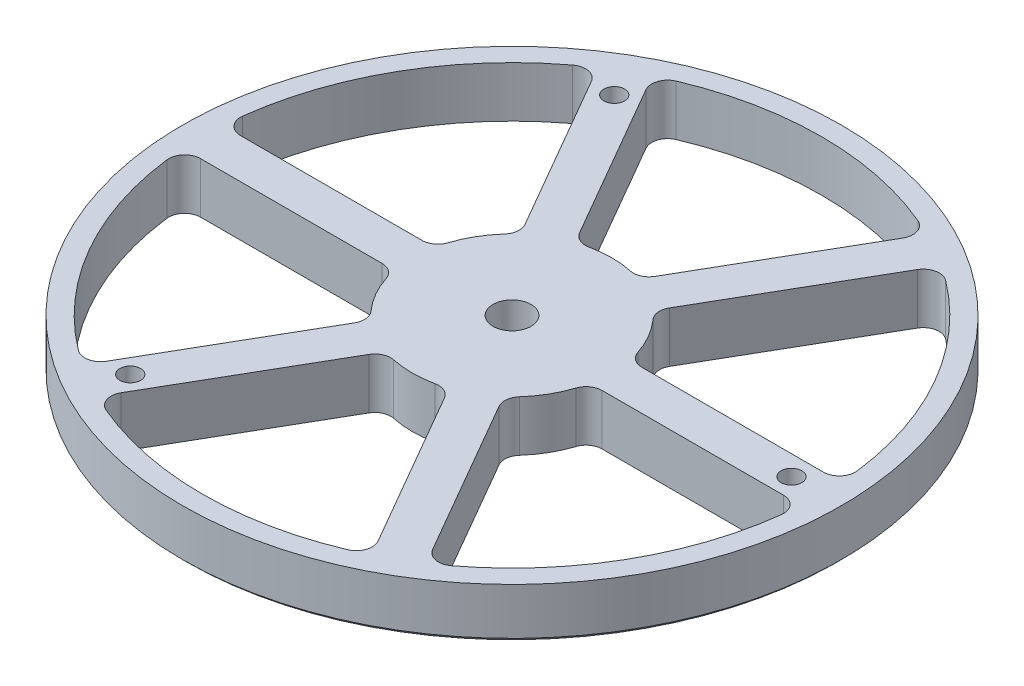
SolidWorks part; units mm, degrees
material "6061-T6 (SS)"
ref_plane "Front Plane" through (0, 0, 0) normal (0, 0, 1) x (1, 0, 0)
ref_plane "Top Plane" through (0, 0, 0) normal (0, 1, 0) x (1, 0, 0)
ref_plane "Right Plane" through (0, 0, 0) normal (1, 0, 0) x (0, 0, -1)
sketch "Sketch2" plane through (0, 0, 0) normal (1, 0, 0) x (0, 0, -1)
  line L0 (0, 0) -> (-82.55, 0)
  line L1 (-82.55, 0) -> (-82.55, 12.7)
  line L2 (-82.55, 12.7) -> (0, 12.7)
  line L5 (0, 12.7) -> (0, 0)
  dimension "D1" = 82.55
  dimension "D2" = 12.7
ref_axis "Axis1" through (0, -0.75, 0) along (0, 1, 0)
revolve "Revolve1" add sketch "Sketch2" angle 360 about axis through (0, -0.75, 0) along (0, 1, 0)
hole_wizard "#6 (0.204) Diameter Hole1" positions "Sketch6" profile "Sketch7" hole size "#6" standard "ANSI Inch" end condition through all
sketch "Sketch6" plane through (0, 12.7, 0) normal (0, 1, 0) x (1, 0, 0)
  line L0 (0, 0) -> (-69.8201, 120.932) construction
  line L2 (0, 0) -> (0, 109.0908) construction
  point P0 (-35, 60.6218)
  dimension "D1" = 30
  dimension "D2" = 70
sketch "Sketch7" plane through (-35, 12.7, -60.6218) normal (1, 0, 0) x (0, 0, 1)
  line L0 (0, 0) -> (0, 12.7)
  line L1 (0, 12.7) -> (2.5908, 12.7)
  line L2 (2.5908, 12.7) -> (2.5908, 0)
  line L5 (2.5908, 0) -> (0, 0)
  line L11 (0, -6.35) -> (0, 107.95) construction
  dimension "Thru Hole Dia." = 5.1816
  dimension "Thru Hole Depth" = 12.7
pattern_circular "CirPattern3" count 3 over 360 about axis through (0, -0.75, 0) along (0, 1, 0) of "#6 (0.204) Diameter Hole1"
sketch "Sketch8" plane through (0, 12.7, 0) normal (0, 1, 0) x (1, 0, 0)
  line L4 (0, 0) -> (0, 93.9995) construction
  line L5 (0, 0) -> (113.8372, 0) construction
  line L6 (-7.9173, 23.7132) -> (-34.3642, 69.5205)
  line L7 (7.9173, 23.7132) -> (34.3642, 69.5205)
  line L8 (0, 0) -> (-35, 60.6218) construction
  arc A0 (-7.9173, 23.7132) -> (7.9173, 23.7132) centre (0, 0) cw
  arc A1 (-34.3642, 69.5205) -> (34.3642, 69.5205) centre (0, 0) cw
  circle A2 centre (0, 0) radius 82.55 construction
  dimension "D1" = 25
  dimension "D2" = 5
  dimension "D3" = 5
extrude "Cut-Extrude1" cut sketch "Sketch8" against normal through all
fillet "Fillet1" radius 4 4 edges at (7.9173, 6.35, -23.7132) (34.3642, 6.35, -69.5205) (-7.9173, 6.35, -23.7132) (-34.3642, 6.35, -69.5205)
pattern_circular "CirPattern4" count 6 over 360 about axis through (0, -0.75, 0) along (0, 1, 0) of "Cut-Extrude1", "Fillet1"
chamfer "Chamfer2" distance 1 angle 45 1 edges at (0, 0, -82.55)
hole_wizard "3/8 (0.375) Diameter Hole1" positions "Sketch9" profile "Sketch11" hole size "3/8" standard "ANSI Inch" end condition through all
sketch "Sketch9" plane through (0, 0, 0) normal (0, -1, 0) x (-1, 0, 0)
  point P0 (0, 0)
sketch "Sketch11" plane through (0, 0, 0) normal (1, 0, 0) x (0, 0, -1)
  line L0 (0, 0) -> (0, 12.7)
  line L1 (0, 12.7) -> (4.7625, 12.7)
  line L2 (4.7625, 12.7) -> (4.7625, 0)
  line L5 (4.7625, 0) -> (0, 0)
  line L11 (0, -6.35) -> (0, 107.95) construction
  dimension "Thru Hole Dia." = 9.525
  dimension "Thru Hole Depth" = 12.7
equation "\"TubeDiameter\" = 6.500in"
equation "\"D1@Sketch2\"=\"TubeDiameter\"/2"
